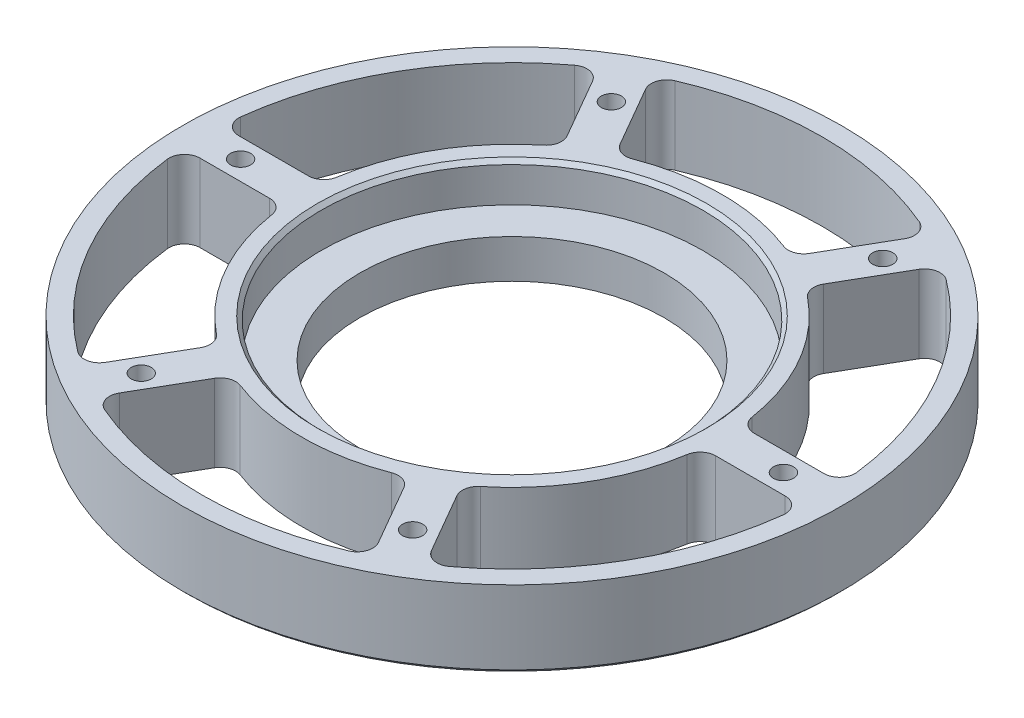
SolidWorks part; units mm, degrees
ref_plane "Front Plane" through (0, 0, 0) normal (0, 0, 1) x (1, 0, 0)
ref_plane "Top Plane" through (0, 0, 0) normal (0, 1, 0) x (1, 0, 0)
ref_plane "Right Plane" through (0, 0, 0) normal (1, 0, 0) x (0, 0, -1)
sketch "Sketch2" plane through (0, 0, 0) normal (1, 0, 0) x (0, 0, -1)
  line L0 (-39.2125, 0) -> (-84.9998, 0)
  line L1 (-84.9998, 0) -> (-84.9998, 20)
  line L2 (-84.9998, 20) -> (-49.2125, 20)
  line L3 (-49.2125, 20) -> (-49.2125, 10)
  line L4 (-49.2125, 10) -> (-39.2125, 10)
  line L5 (-39.2125, 10) -> (-39.2125, 0)
  dimension "D1" = 84.9998
  dimension "D2" = 20
  dimension "D3" = 10
  dimension "D4" = 49.2125
  dimension "D5" = 10
ref_axis "Axis1" through (0, -0.75, 0) along (0, 1, 0)
revolve "Revolve1" add sketch "Sketch2" angle 360 about axis through (0, -0.75, 0) along (0, 1, 0)
hole_wizard "#6 (0.204) Diameter Hole1" positions "Sketch6" profile "Sketch7" hole size "#6" standard "ANSI Inch" end condition through all
sketch "Sketch6" plane through (0, 20, 0) normal (0, 1, 0) x (1, 0, 0)
  line L0 (0, 0) -> (-69.8201, 120.932) construction
  line L2 (0, 0) -> (0, 109.0908) construction
  point P0 (-35, 60.6218)
  dimension "D1" = 30
  dimension "D2" = 70
sketch "Sketch7" plane through (-35, 20, -60.6218) normal (1, 0, 0) x (0, 0, 1)
  line L0 (0, 0) -> (0, 20)
  line L1 (0, 20) -> (2.5908, 20)
  line L2 (2.5908, 20) -> (2.5908, 0)
  line L5 (2.5908, 0) -> (0, 0)
  line L11 (0, -6.35) -> (0, 107.95) construction
  dimension "Thru Hole Dia." = 5.1816
  dimension "Thru Hole Depth" = 20
pattern_circular "CirPattern3" count 6 over 360 about axis through (0, -0.75, 0) along (0, 1, 0) of "#6 (0.204) Diameter Hole1"
sketch "Sketch8" plane through (0, 20, 0) normal (0, 1, 0) x (1, 0, 0)
  line L0 (-35.5916, 71.6464) -> (-22.6606, 49.2493)
  line L1 (35.5916, 71.6464) -> (22.6606, 49.2493)
  line L2 (0, 0) -> (-35, 60.6218) construction
  line L4 (0, 0) -> (0, 93.9995) construction
  arc A0 (-22.6606, 49.2493) -> (22.6606, 49.2493) centre (0, 0) cw
  arc A1 (-35.5916, 71.6464) -> (35.5916, 71.6464) centre (0, 0) cw
  circle A2 centre (0, 0) radius 49.2125 construction
  circle A3 centre (0, 0) radius 84.9998 construction
  dimension "D1" = 5
  dimension "D2" = 5
  dimension "D3" = 5
extrude "Cut-Extrude1" cut sketch "Sketch8" against normal through all
fillet "Fillet1" radius 4 4 edges at (35.5916, 10, -71.6464) (22.6606, 10, -49.2493) (-35.5916, 10, -71.6464) (-22.6606, 10, -49.2493)
pattern_circular "CirPattern4" count 6 over 360 about axis through (0, -0.75, 0) along (0, 1, 0) of "Cut-Extrude1", "Fillet1"
chamfer "Chamfer1" distance 1 angle 45 1 edges at (0, 20, -49.2125)
chamfer "Chamfer2" distance 1 angle 45 1 edges at (0, 0, -84.9998)
